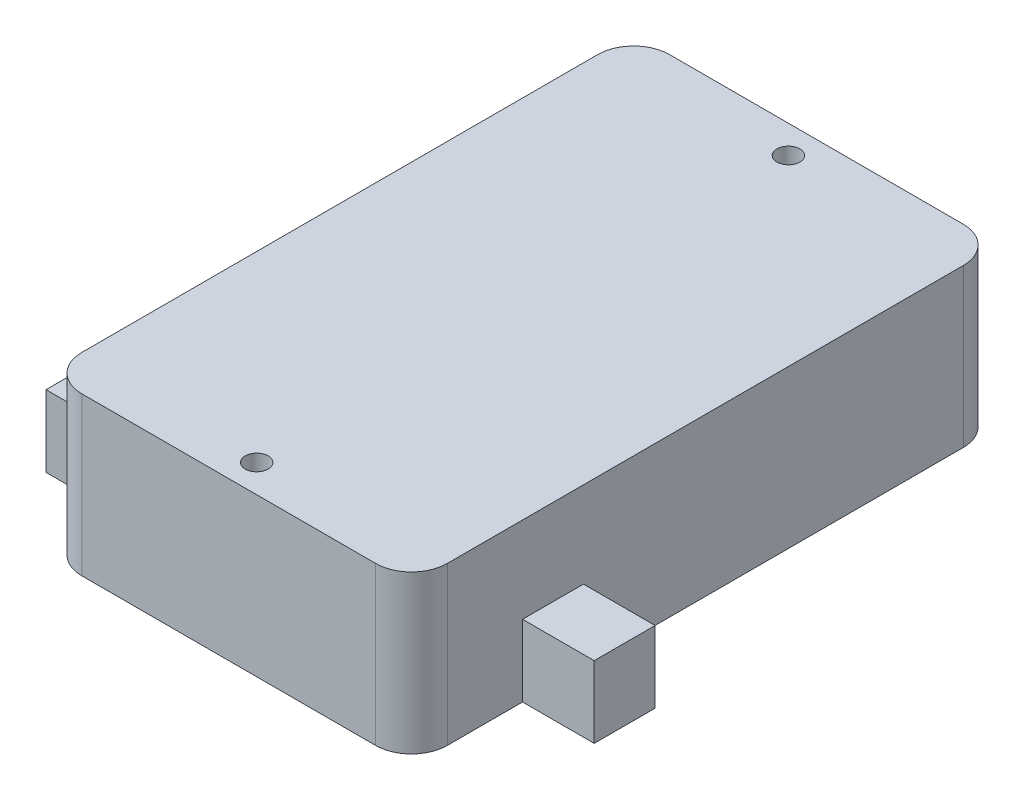
SolidWorks part; units mm, degrees
ref_plane "Front Plane" through (0, 0, 0) normal (0, 0, 1) x (1, 0, 0)
ref_plane "Top Plane" through (0, 0, 0) normal (0, 1, 0) x (1, 0, 0)
ref_plane "Right Plane" through (0, 0, 0) normal (1, 0, 0) x (0, 0, -1)
sketch "Sketch1" plane through (0, 0, 0) normal (0, 1, 0) x (1, 0, 0)
  line L0 (-25.5, 0) -> (25.5, 0) construction
  line L1 (-25.5, -41) -> (25.5, -41)
  line L2 (-25.5, -41) -> (-25.5, 41)
  line L3 (-25.5, 41) -> (25.5, 41)
  line L4 (25.5, -41) -> (25.5, 41)
  line L5 (-25.5, -41) -> (25.5, 41) construction
  line L6 (-25.5, 41) -> (25.5, -41) construction
  line L7 (11.5, -41) -> (11.5, -56) construction
  line L8 (25.5, -25.5) -> (35.5, -25.5)
  line L9 (25.5, -25.5) -> (25.5, -17)
  line L10 (25.5, -17) -> (35.5, -17)
  line L11 (35.5, -25.5) -> (35.5, -17)
  line L12 (25.5, -25.5) -> (35.5, -17) construction
  line L13 (25.5, -17) -> (35.5, -25.5) construction
  line L14 (-25.5, -5) -> (-35.5, -5)
  line L15 (-25.5, -5) -> (-25.5, -31)
  line L16 (-25.5, -31) -> (-35.5, -31)
  line L17 (-35.5, -5) -> (-35.5, -31)
  circle A0 centre (0, -37.1) radius 1.6
  circle A1 centre (0, 37.1) radius 1.6
  point P0 (0, 0)
  point P12 (30.5, -21.25)
  dimension "D3" = 3.2
  dimension "D1" = 51
  dimension "D2" = 82
  dimension "D4" = 3.9
  dimension "D5" = 8.5
  dimension "D6" = 24
  dimension "D7" = 10
  dimension "D8" = 26
  dimension "D9" = 36
  dimension "D10" = 10
  dimension "D11" = 14
  dimension "D12" = 15
extrude "Boss-Extrude1" add sketch "Sketch1" along normal blind 22 contours L1 L4 L3 L2 A0 A1 region at (0, 0, 0)
extrude "Boss-Extrude2" add sketch "Sketch1<3>" along normal blind 10 contours L8 L11 L10 L4 | L14 L17 L16 L2 region at (-30.5, 0, 18) region at (30.5, 0, 21.25)
sketch "Sketch1<3>" plane through (0, 0, 0) normal (0, 1, 0) x (1, 0, 0) same geometry as "Sketch1"
fillet "Fillet1" radius 5 4 edges at (-25.5, 11, -41) (25.5, 11, -41) (25.5, 11, 41) (-25.5, 11, 41)
equation "\"D4@Sketch1\"=2.2+1.7"
